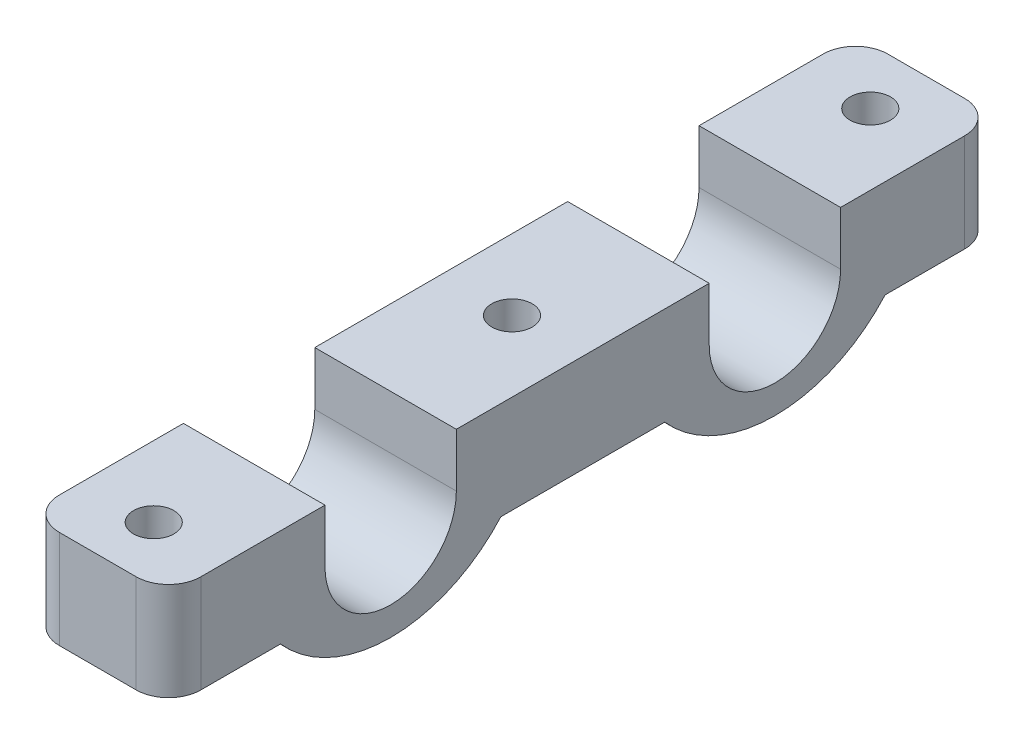
SolidWorks part; units mm, degrees
ref_plane "Front Plane" through (0, 0, 0) normal (0, 0, 1) x (1, 0, 0)
ref_plane "Top Plane" through (0, 0, 0) normal (0, 1, 0) x (1, 0, 0)
ref_plane "Right Plane" through (0, 0, 0) normal (1, 0, 0) x (0, 0, -1)
sketch "Sketch2" plane through (0, 0, 0) normal (1, 0, 0) x (0, 0, -1)
  line L0 (-15.24, 0) -> (15.24, 0) construction
  line L1 (-16.24, 0) -> (-54.9202, 0) construction
  line L2 (16.24, 0) -> (78.76, 0) construction
  line L3 (0, 0) -> (95, 0) construction
  line L4 (111.24, 0) -> (149.9202, 0) construction
  line L5 (-27.24, -11) -> (-54.9202, -11)
  line L6 (27.24, -11) -> (67.76, -11)
  line L7 (122.24, -11) -> (149.9202, -11)
  line L8 (-54.9202, 0) -> (-54.9202, -11)
  line L9 (149.9202, 0) -> (149.9202, -11)
  line L10 (-54.9202, 0) -> (-54.9202, 13.24)
  line L11 (-54.9202, 13.24) -> (-16.24, 13.24)
  line L12 (-16.24, 13.24) -> (-16.24, 0)
  line L13 (16.24, 0) -> (16.24, 13.24)
  line L14 (16.24, 13.24) -> (78.76, 13.24)
  line L15 (78.76, 13.24) -> (78.76, 0)
  line L16 (111.24, 0) -> (111.24, 13.24)
  line L17 (111.24, 13.24) -> (149.9202, 13.24)
  line L18 (149.9202, 13.24) -> (149.9202, 0)
  line L19 (0, -16.24) -> (0, -23.24) construction
  line L20 (47.5, 0) -> (47.5, -11) construction
  arc A0 (-15.24, 0) -> (15.24, 0) centre (0, 0) ccw construction
  arc A1 (-16.24, 0) -> (16.24, 0) centre (0, 0) ccw
  arc A2 (79.76, 0) -> (110.24, 0) centre (95, 0) ccw construction
  arc A3 (78.76, 0) -> (111.24, 0) centre (95, 0) ccw
  arc A8 (-27.24, -11) -> (27.24, -11) centre (0, 13.1912) ccw
  arc A9 (67.76, -11) -> (122.24, -11) centre (95, 13.1912) ccw
  point P17 (69.9192, -11.3325)
  point P31 (70.1288, -10.9008)
  dimension "D6" = 11
  dimension "D11" = 7
  dimension "D1" = 30.48
  dimension "D3" = 95
  dimension "D7" = 11
  dimension "D8" = 11
  dimension "D9" = 13.24
  dimension "D10" = 204.8404
  dimension "D2" = 1
  dimension "D4" = 1
extrude "Boss-Extrude1" add sketch "Sketch2" along normal blind 35
sketch "Sketch3" plane through (0, 13.24, 0) normal (0, 1, 0) x (1, 0, 0)
  line L0 (0, -54.9202) -> (0, -27.24) construction
  line L1 (0, -54.9202) -> (0, -27.24) construction
  line L3 (35, -54.9202) -> (0, -54.9202) construction
  line L5 (35, 78.76) -> (35, 16.24) construction
  line L8 (35, -54.9202) -> (0, -54.9202) construction
  line L9 (35, -16.24) -> (35, -54.9202) construction
  line L10 (0, 78.76) -> (0, 16.24) construction
  line L11 (35, 16.24) -> (0, 16.24) construction
  line L16 (35, 16.24) -> (0, 16.24) construction
  line L18 (35, 78.76) -> (35, 16.24) construction
  line L19 (0, 78.76) -> (0, 16.24) construction
  line L24 (0, 47.5) -> (35, 47.5) construction
  line L25 (35, 78.76) -> (0, 78.76) construction
  circle A0 centre (17.5, -41.0801) radius 5
  circle A1 centre (17.5, 136.0801) radius 5
  circle A2 centre (17.5, 47.5) radius 5
  point P6 (0, -41.0801)
  point P14 (17.5, -54.9202)
  dimension "D1" = 10
extrude "Cut-Extrude1" cut sketch "Sketch3" against normal up to next
sketch "Sketch4" plane through (0, -11, 0) normal (0, -1, 0) x (1, 0, 0)
  circle A0 centre (17.5, -47.5) radius 10.5
  circle A1 centre (17.5, -136.0801) radius 10.5
  circle A2 centre (17.5, 41.0801) radius 10.5
  dimension "D1" = 21
extrude "Cut-Extrude2" cut sketch "Sketch4" against normal blind 10
fillet "Fillet1" radius 8 4 edges at (35, 1.12, 54.9202) (0, 1.12, 54.9202) (35, 1.12, -149.9202) (0, 1.12, -149.9202)
